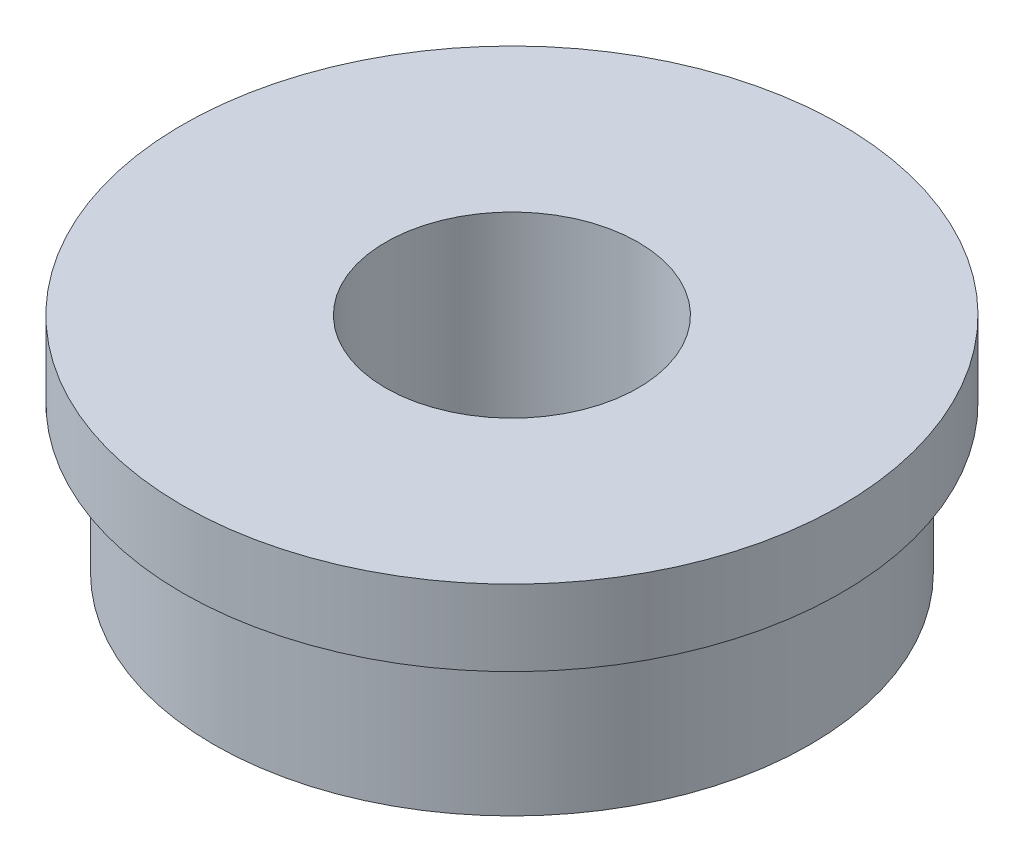
SolidWorks part; units mm, degrees
material "Chrome Stainless Steel"
ref_plane "Front Plane" through (0, 0, 0) normal (0, 0, 1) x (1, 0, 0)
ref_plane "Top Plane" through (0, 0, 0) normal (0, 1, 0) x (1, 0, 0)
ref_plane "Right Plane" through (0, 0, 0) normal (1, 0, 0) x (0, 0, -1)
sketch "Sketch5" plane through (0, 0, 0) normal (0, 1, 0) x (1, 0, 0)
  circle A0 centre (0, 0) radius 4.7625
  circle A1 centre (0, 0) radius 11.1125
  circle A2 centre (0, 0) radius 12.3031
  dimension "D1" = 24.6062
  dimension "D2" = 9.525
  dimension "D3" = 22.225
sketch "Sketch2" plane through (0, 0, 0) normal (0, 1, 0) x (1, 0, 0)
  circle A0 centre (0, 0) radius 11.1125
  circle A1 centre (0, 0) radius 11.1125 construction
extrude "Boss-Extrude1" add sketch "Sketch2" along normal blind 7.1437
sketch "Sketch3" plane through (0, 7.1437, 0) normal (0, 1, 0) x (1, 0, 0)
  circle A0 centre (0, 0) radius 12.3031
  circle A2 centre (0, 0) radius 12.3031 construction
extrude "Boss-Extrude2" add sketch "Sketch3" against normal blind 1.5875
sketch "Sketch4" plane through (0, 0, 0) normal (0, 1, 0) x (1, 0, 0)
  circle A0 centre (0, 0) radius 4.7625
  circle A1 centre (0, 0) radius 4.7625 construction
extrude "Cut-Extrude2" cut sketch "Sketch4" along normal through all both and the other way through all
other "Move Face1" face at (0, 5.5563, 11.1125) face at (0, 0, 4.7625) offset 1.27 parameters "D1"=1.27
other "Move Face2" face at (0, 4.2862, 12.3031) face at (0, -1.27, 11.1125) offset 0.127 parameters "D1"=0.127
chamfer "Chamfer1" distance 0.3969 angle 45 1 edges at (0, 4.2862, 11.2395)
